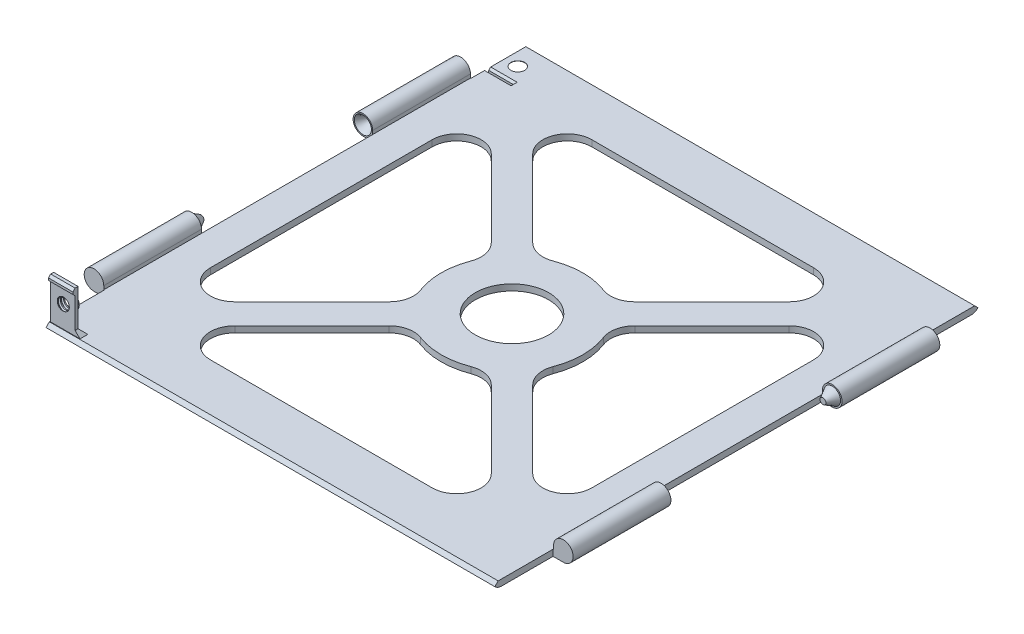
SolidWorks part; units mm, degrees
material "6061 Alloy"
ref_plane "Front Plane" through (0, 0, 0) normal (0, 0, 1) x (1, 0, 0)
ref_plane "Top Plane" through (0, 0, 0) normal (0, 1, 0) x (1, 0, 0)
ref_plane "Right Plane" through (0, 0, 0) normal (1, 0, 0) x (0, 0, -1)
sketch "X-Axis" plane through (0, 0, 0) normal (0, 1, 0) x (1, 0, 0)
  line L2 (-10, 0) -> (10, 0)
  point P3 (0, 0)
  dimension "D1" = 20
sketch "Y-Axis" plane through (0, 0, 0) normal (0, 1, 0) x (1, 0, 0)
  line L0 (0, -10) -> (0, 10)
  dimension "D1" = 20
sketch "Z-Axis" plane through (0, 0, 0) normal (1, 0, 0) x (0, 0, -1)
  line L0 (0, 10) -> (0, -10)
  line L1 (0, 55) -> (0, -55) construction
  point P5 (0, 0)
  dimension "D1" = 20
ref_axis "Axis1" through (0, 0, 0) along (0, 1, 0)
sketch "Sketch1" plane through (0, 0, 0) normal (0, 1, 0) x (1, 0, 0)
  line L0 (-10.4535, 14.6961) -> (-26.2218, 30.4645)
  line L1 (-46, -46) -> (46, -46) construction
  line L2 (-46, -46) -> (-46, 46) construction
  line L3 (-46, 46) -> (46, 46) construction
  line L4 (46, -46) -> (46, 46) construction
  line L5 (-46, -46) -> (46, 46) construction
  line L6 (-46, 46) -> (46, -46) construction
  line L7 (-22.6863, 39) -> (22.6863, 39)
  line L8 (26.2218, 30.4645) -> (10.4535, 14.6961)
  line L9 (30.4645, -26.2218) -> (14.6961, -10.4535)
  line L10 (14.6961, 10.4535) -> (30.4645, 26.2218)
  line L11 (39, 22.6863) -> (39, -22.6863)
  line L12 (-26.2218, -30.4645) -> (-10.4535, -14.6961)
  line L13 (10.4535, -14.6961) -> (26.2218, -30.4645)
  line L14 (22.6863, -39) -> (-22.6863, -39)
  line L15 (-30.4645, 26.2218) -> (-14.6961, 10.4535)
  line L16 (-14.6961, -10.4535) -> (-30.4645, -26.2218)
  line L17 (-39, -22.6863) -> (-39, 22.6863)
  line L19 (46, -50) -> (-46, -50)
  line L20 (46, -50) -> (46, 50)
  line L21 (46, 50) -> (-46, 50)
  line L22 (-46, -50) -> (-46, 50)
  line L23 (46, -50) -> (-46, 50) construction
  line L24 (46, 50) -> (-46, -50) construction
  circle A0 centre (0, 0) radius 7.5
  arc A1 (-5.1441, 13.5569) -> (5.1441, 13.5569) centre (0, 0) cw
  arc A2 (-5.1441, 13.5569) -> (-10.4535, 14.6961) centre (-6.9179, 18.2316) cw
  arc A3 (5.1441, 13.5569) -> (10.4535, 14.6961) centre (6.9179, 18.2316) ccw
  arc A4 (22.6863, 39) -> (26.2218, 30.4645) centre (22.6863, 34) cw
  arc A5 (-26.2218, 30.4645) -> (-22.6863, 39) centre (-22.6863, 34) cw
  arc A6 (13.5569, -5.1441) -> (14.6961, -10.4535) centre (18.2316, -6.9179) ccw
  arc A7 (13.5569, 5.1441) -> (13.5569, -5.1441) centre (0, 0) cw
  arc A8 (13.5569, 5.1441) -> (14.6961, 10.4535) centre (18.2316, 6.9179) cw
  arc A9 (30.4645, 26.2218) -> (39, 22.6863) centre (34, 22.6863) cw
  arc A10 (39, -22.6863) -> (30.4645, -26.2218) centre (34, -22.6863) cw
  arc A11 (-5.1441, -13.5569) -> (-10.4535, -14.6961) centre (-6.9179, -18.2316) ccw
  arc A12 (5.1441, -13.5569) -> (-5.1441, -13.5569) centre (0, 0) cw
  arc A13 (5.1441, -13.5569) -> (10.4535, -14.6961) centre (6.9179, -18.2316) cw
  arc A14 (26.2218, -30.4645) -> (22.6863, -39) centre (22.6863, -34) cw
  arc A15 (-22.6863, -39) -> (-26.2218, -30.4645) centre (-22.6863, -34) cw
  arc A16 (-13.5569, 5.1441) -> (-14.6961, 10.4535) centre (-18.2316, 6.9179) ccw
  arc A17 (-13.5569, -5.1441) -> (-13.5569, 5.1441) centre (0, 0) cw
  arc A18 (-13.5569, -5.1441) -> (-14.6961, -10.4535) centre (-18.2316, -6.9179) cw
  arc A19 (-30.4645, -26.2218) -> (-39, -22.6863) centre (-34, -22.6863) cw
  arc A20 (-39, 22.6863) -> (-30.4645, 26.2218) centre (-34, 22.6863) cw
  point P0 (0, 0)
  point P59 (0, 0)
  dimension "D3" = 15
  dimension "D6" = 7
  dimension "D8" = 5
  dimension "D1" = 92
  dimension "D2" = 92
  dimension "D4" = 6
  dimension "D5" = 6
  dimension "D7" = 39
  dimension "D10" = 100
  dimension "D9" = 4
extrude "Boss-Extrude1" add sketch "Sketch1" along normal blind 1.27
ref_plane "Plane3" through (0, 0, 17.5) normal (0, 0, 1) x (1, 0, 0)
sketch "Sketch6" plane through (0, 0, 17.5) normal (0, 0, 1) x (1, 0, 0)
  line L0 (46, 2) -> (46, 0)
  line L1 (46, 0) -> (48, 0)
  line L2 (0, 0) -> (0, 69.0457) construction
  arc A0 (46, 2) -> (48, 0) centre (48, 2) cw
  dimension "D1" = 50
extrude "Boss-Extrude3" add sketch "Sketch6" along normal blind 20
sketch "Sketch25" plane through (0, 0, 17.5) normal (0, 0, 1) x (1, 0, 0)
  line L0 (-46, 0) -> (-48, 0)
  line L1 (-46, 1.27) -> (-46, 0)
  line L4 (-46, 2) -> (-46, 1.27)
  arc A0 (-46, 2) -> (-48, 0) centre (-48, 2) ccw
  dimension "D1" = 50
extrude "Boss-Extrude10" add sketch "Sketch25" along normal up to surface (20 mm away) up to face at (47.1036, 1.4211, 37.5)
mirror "Mirror1" about plane through (0, 0, 0) normal (0, 0, 1) of "Boss-Extrude10", "Boss-Extrude3"
sketch "Sketch16" plane through (0, 0, 17.5) normal (0, 0, -1) x (-1, 0, 0)
  circle A0 centre (-48, 2) radius 1.75
  dimension "D1" = 3.5
sketch "Sketch17" plane through (0, 0, -17.5) normal (0, 0, 1) x (1, 0, 0)
  circle A0 centre (48, 2) radius 1.7
  dimension "D1" = 3.4
extrude "Cut-Extrude5" cut sketch "Sketch16" against normal blind 2 draft 30 contours A0
extrude "Boss-Extrude7" add sketch "Sketch17" along normal blind 1.9 draft 30
sketch "Sketch21" plane through (46, 0, 0) normal (1, 0, 0) x (0, 0, -1)
  line L0 (-50, 0) -> (-47.5953, 2.4047) construction
  line L3 (-50, 0) -> (-37.5, 0) construction
  line L4 (-50, 1.27) -> (-50, 0) construction
  line L5 (-50, 1.27) -> (-37.5, 1.27) construction
  arc A0 (-50, 2) -> (-48, 0) centre (-48, 2) ccw
  dimension "D2" = 2
  dimension "D1" = 45
sketch "Sketch28" plane through (0, 0, -17.5) normal (0, 0, 1) x (1, 0, 0)
  circle A0 centre (-48, 2) radius 1.75
  dimension "D1" = 3.5
extrude "Cut-Extrude11" cut sketch "Sketch28" against normal blind 2 draft 30
sketch "Sketch29" plane through (0, 0, 17.5) normal (0, 0, -1) x (-1, 0, 0)
  circle A0 centre (48, 2) radius 1.7
  dimension "D1" = 3.4
extrude "Boss-Extrude12" add sketch "Sketch29" along normal blind 1.9 draft 30
sketch "Sketch22" plane through (46, 0, 0) normal (1, 0, 0) x (0, 0, -1)
  line L0 (-48, 2) -> (-50.6263, -0.6263)
  line L2 (-50, 1.27) -> (-37.5, 1.27) construction
  point P0 (-48, 2)
  dimension "D1" = 45
extrude "Cut-Extrude7" cut sketch "Sketch22" against normal through all and the other way through all flip side to cut
extrude "Cut-Extrude8" cut sketch "Sketch21" against normal through all and the other way through all flip side to cut
sketch "Sketch24" plane through (0, 1.27, 0) normal (0, 1, 0) x (1, 0, 0)
  line L0 (46, -37.5) -> (50, -37.5) construction
  line L1 (46, -49.4142) -> (45.9, -49.4142)
  line L2 (46, -49.4142) -> (46, -37.5)
  line L3 (46, -37.5) -> (45.9, -37.5)
  line L4 (45.9, -49.4142) -> (45.9, -37.5)
  line L5 (-46, -49.4142) -> (46, -49.4142) construction
  line L6 (-46, -37.5) -> (-45.9, -37.5)
  line L7 (-46, -37.5) -> (-46, -49.4142)
  line L8 (-46, -49.4142) -> (-45.9, -49.4142)
  line L9 (-45.9, -37.5) -> (-45.9, -49.4142)
  dimension "D1" = 0.1
  dimension "D2" = 0.1
extrude "Cut-Extrude9" cut sketch "Sketch24" against normal through all
mirror "Mirror2" about plane through (0, 0, 0) normal (0, 0, 1) of "Cut-Extrude8", "Cut-Extrude9", "Cut-Extrude7"
sketch "Sketch30" plane through (0, 1.27, 0) normal (0, 1, 0) x (1, 0, 0)
  line L1 (-40.73, -48.03) -> (-45.73, -48.03)
  line L2 (-40.73, -48.03) -> (-40.73, -48.63)
  line L3 (-40.73, -48.63) -> (-45.73, -48.63)
  line L4 (-45.73, -48.03) -> (-45.73, -48.63)
  line L5 (45.9, -48.73) -> (-45.9, -48.73) construction
  line L7 (-45.9, -48.73) -> (-45.9, -37.5) construction
  dimension "D1" = 0.17
  dimension "D2" = 0.6
  dimension "D3" = 0.1
  dimension "D4" = 5
extrude "Boss-Extrude13" add sketch "Sketch30" along normal blind 8.5
sketch "Sketch31" plane through (-45.73, 0, 0) normal (-1, 0, 0) x (0, 0, 1)
  line L0 (48.63, 9.77) -> (48.63, 8.4016)
  line L1 (48.63, 9.77) -> (48.63, 1.27) construction
  line L2 (48.63, 8.4016) -> (49.0892, 8.8608)
  line L3 (49.0892, 8.8608) -> (49.0892, 9.3108)
  line L4 (49.0892, 9.3108) -> (48.63, 9.77)
  line L5 (48.63, 9.77) -> (48.03, 9.77) construction
  point P5 (49.0892, 9.0858)
  point P8 (48.33, 9.77)
  dimension "D1" = 0.45
  dimension "D2" = 45
  dimension "D3" = 45
  dimension "D4" = 0.6842
  dimension "D5" = 8.5
extrude "Boss-Extrude14" add sketch "Sketch31" against normal up to surface (5 mm away) up to face at (-40.73, 5.52, 48.33)
sketch "Sketch32" plane through (0, 1.27, 0) normal (0, 1, 0) x (1, 0, 0)
  line L0 (45.9, 49.4142) -> (-45.9, 49.4142) construction
  line L1 (-45.98, 41.1392) -> (-40.48, 41.1392)
  line L2 (-45.98, 41.1392) -> (-45.98, 40.6892)
  line L3 (-45.98, 40.6892) -> (-40.48, 40.6892)
  line L4 (-40.48, 41.1392) -> (-40.48, 40.6892)
  point P4 (-45.98, 40.9142)
  dimension "D1" = 45.98
  dimension "D2" = 0.45
  dimension "D3" = 8.5
  dimension "D4" = 5.5
extrude "Cut-Extrude12" cut sketch "Sketch32" against normal through all
chamfer "Chamfer1" distance 0.4 angle 45 2 edges at (-43.19, 1.27, -40.6892) (-43.19, 1.27, -41.1392)
sketch "Sketch33" plane through (0, 0, 48.03) normal (0, 0, -1) x (-1, 0, 0)
  line L0 (40.73, 9.77) -> (45.73, 9.77) construction
  line L5 (40.73, 9.3108) -> (40.73, 8.8608) construction
  circle A0 centre (43.23, 5.5858) radius 1.75
  point P4 (43.23, 9.77)
  point P7 (40.73, 9.0858)
  dimension "D1" = 3.5
  dimension "D2" = 3.5
extrude "Boss-Extrude15" add sketch "Sketch33" along normal blind 1
sketch "Sketch34" plane through (0, 0, 47.03) normal (0, 0, -1) x (-1, 0, 0)
  circle A0 centre (43.23, 5.5858) radius 1.1301
  dimension "D1" = 2.2603
extrude "Cut-Extrude13" cut sketch "Sketch34" against normal through all
ref_plane "Plane4" through (0, 0, 45.03) normal (0, 0, -1) x (-1, 0, 0)
sketch "Sketch35" plane through (0, 0, 45.03) normal (0, 0, -1) x (-1, 0, 0)
  circle A0 centre (43.23, 5.5858) radius 1.1301 construction
  circle A1 centre (43.23, 5.5858) radius 1.1301
curve "Helix/Spiral1" pitch 0.635 height 9.525 radius 1.1301 centre (-43.23, 5.5858, 45.03) axis (0, 0, 1) start towards (-1, 0, 0)
ref_axis "Axis2" through (-43.23, 5.5858, 47.03) along (0, 0, 1)
ref_plane "Plane5" through (-44.3601, 5.5858, 45.03) normal (0, -0.996, 0.0891) x (-1, 0, 0)
sketch "Sketch36" plane through (-44.3601, 5.5858, 45.03) normal (0, -0.996, 0.0891) x (-1, 0, 0)
  line L0 (0.2923, 0.04) -> (0.2923, -0.04)
  line L1 (0.2923, -0.04) -> (-0.1301, -0.2839)
  line L2 (-0.1301, -0.2839) -> (-0.1301, 0.2839)
  line L3 (-0.1301, 0.2839) -> (0.2923, 0.04)
  line L4 (-1.1301, -1.9921) -> (-1.1301, -2.9881) construction
  point P0 (0, 0)
  point P8 (0.2923, 0)
  dimension "D1" = 60
  dimension "D2" = 60
  dimension "D3" = 1.4224
  dimension "D4" = 0.08
  dimension "D5" = 1
sweep "Cut-Sweep1" cut profiles "Sketch36" path "Helix/Spiral1"
sketch "Sketch37" plane through (0, 1.27, 0) normal (0, 1, 0) x (1, 0, 0)
  line L0 (-40.48, 41.5392) -> (-45.98, 41.5392) construction
  line L1 (-40.48, 40.2892) -> (-40.48, 41.5392) construction
  circle A0 centre (-43.23, 44.4142) radius 1.4046
  point P5 (-43.23, 41.5392)
  point P6 (-40.48, 40.9142)
  dimension "D1" = 2.8092
  dimension "D2" = 5.5
  dimension "D3" = 3.5
extrude "Cut-Extrude14" cut sketch "Sketch37" against normal through all
ref_axis "Axis3" through (-43.23, 0, -44.4142) along (0, 1, 0)
ref_plane "Plane6" through (-43.23, 0, 0) normal (-1, 0, 0) x (0, 0, 1)
sketch "Sketch38" plane through (-43.23, 0, 0) normal (-1, 0, 0) x (0, 0, 1)
  line L0 (-44.4142, 1.9632) -> (-44.4142, 1.2192) construction
  line L1 (-44.4142, 0) -> (-44.4142, 1.27) construction
  line L2 (-44.4142, 1.2192) -> (-46.7199, 1.2192)
  line L3 (-46.7199, 1.2192) -> (-47.7797, 0)
  line L4 (-48, 0) -> (-41.1392, 0) construction
  line L5 (-47.7797, 0) -> (-44.4142, 0)
  line L6 (-44.4142, 0) -> (-44.4142, 1.2192)
  dimension "D1" = 6.731
  dimension "D2" = 49
  dimension "D3" = 1.2192
revolve "Cut-Revolve1" cut sketch "Sketch38" angle 360 about L0
chamfer "Chamfer2" distance 1 angle 45 2 edges at (-43.23, 1.27, 48.03) (-40.73, 1.27, 48.33)
equation "\"D3@Sketch37\"=\"D2@Sketch33\""
equation "\"D3@Sketch32\"=\"D1@Boss-Extrude13\""
